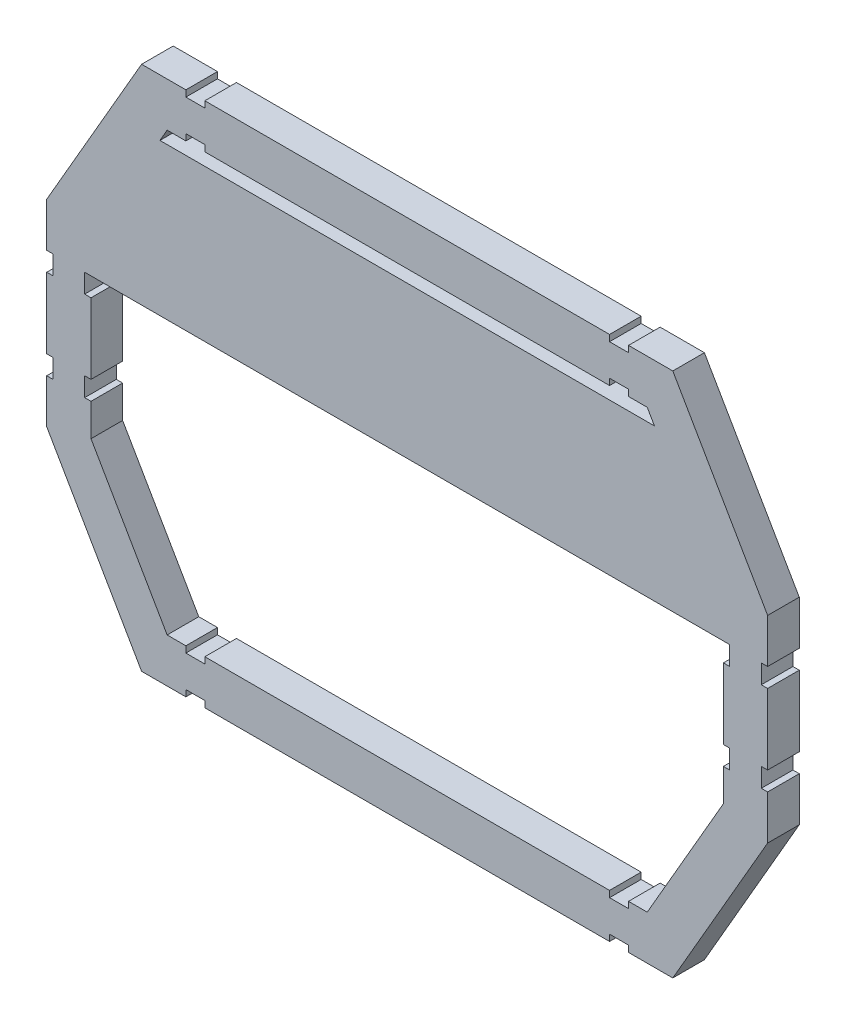
SolidWorks part; units mm, degrees
ref_plane "Plan de face" through (0, 0, 0) normal (0, 0, 1) x (1, 0, 0)
ref_plane "Plan de dessus" through (0, 0, 0) normal (0, 1, 0) x (1, 0, 0)
ref_plane "Plan de droite" through (0, 0, 0) normal (1, 0, 0) x (0, 0, -1)
sketch "Esquisse1" plane through (0, 0, 0) normal (0, 0, 1) x (1, 0, 0)
  line L0 (82.5398, -153.6268) -> (18.5398, -153.6268)
  line L1 (18.5398, -153.6268) -> (18.5398, -152.6268)
  line L2 (18.5398, -152.6268) -> (15.5398, -152.6268)
  line L3 (15.5398, -152.6268) -> (15.5398, -153.6268)
  line L4 (15.5398, -153.6268) -> (8.5398, -153.6268)
  line L5 (8.5398, -153.6268) -> (-6.4602, -127.646)
  line L6 (-6.4602, -127.646) -> (-6.4602, -120.646)
  line L7 (-6.4602, -120.646) -> (-5.4602, -120.646)
  line L8 (-5.4602, -120.646) -> (-5.4602, -117.646)
  line L9 (-5.4602, -117.646) -> (-6.4602, -117.646)
  line L10 (-6.4602, -117.646) -> (-6.4602, -106.4691)
  line L11 (50.5398, -153.6268) -> (50.5398, -70.4883) construction
  line L12 (100.5398, -112.0576) -> (0.5398, -112.0576) construction
  line L13 (1.0398, -140.6364) -> (50.5398, -112.0576) construction
  line L14 (0.5398, -106.4691) -> (0.5398, -117.646)
  line L15 (0.5398, -117.646) -> (-0.4602, -117.646)
  line L16 (-0.4602, -117.646) -> (-0.4602, -120.646)
  line L17 (-0.4602, -120.646) -> (0.5398, -120.646)
  line L18 (0.5398, -120.646) -> (0.5398, -125.7704)
  line L19 (0.5398, -125.7704) -> (12.5813, -146.6268)
  line L20 (12.5813, -146.6268) -> (15.5398, -146.6268)
  line L21 (15.5398, -146.6268) -> (15.5398, -147.6268)
  line L22 (15.5398, -147.6268) -> (18.5398, -147.6268)
  line L23 (18.5398, -147.6268) -> (18.5398, -146.6268)
  line L24 (18.5398, -146.6268) -> (82.5398, -146.6268)
  line L25 (1.0398, -83.4787) -> (50.5398, -112.0576) construction
  line L26 (18.5398, -77.4883) -> (82.5398, -77.4883)
  line L27 (18.5398, -76.4883) -> (18.5398, -77.4883)
  line L28 (15.5398, -76.4883) -> (18.5398, -76.4883)
  line L29 (15.5398, -77.4883) -> (15.5398, -76.4883)
  line L30 (12.5813, -77.4883) -> (15.5398, -77.4883)
  line L31 (88.4984, -77.4883) -> (89.642, -79.4691)
  line L33 (-0.4602, -103.4691) -> (0.5398, -103.4691)
  line L34 (-0.4602, -106.4691) -> (-0.4602, -103.4691)
  line L35 (0.5398, -106.4691) -> (-0.4602, -106.4691)
  line L36 (-5.4602, -106.4691) -> (-6.4602, -106.4691)
  line L37 (-5.4602, -103.4691) -> (-5.4602, -106.4691)
  line L38 (-6.4602, -103.4691) -> (-5.4602, -103.4691)
  line L39 (-6.4602, -96.4691) -> (-6.4602, -103.4691)
  line L40 (8.5398, -70.4883) -> (-6.4602, -96.4691)
  line L41 (15.5398, -70.4883) -> (8.5398, -70.4883)
  line L42 (15.5398, -71.4883) -> (15.5398, -70.4883)
  line L43 (18.5398, -71.4883) -> (15.5398, -71.4883)
  line L44 (18.5398, -70.4883) -> (18.5398, -71.4883)
  line L45 (82.5398, -70.4883) -> (18.5398, -70.4883)
  line L46 (100.0398, -83.4787) -> (50.5398, -112.0576) construction
  line L47 (100.0398, -140.6364) -> (50.5398, -112.0576) construction
  line L48 (82.5398, -70.4883) -> (82.5398, -71.4883)
  line L49 (82.5398, -71.4883) -> (85.5398, -71.4883)
  line L50 (85.5398, -71.4883) -> (85.5398, -70.4883)
  line L51 (85.5398, -70.4883) -> (92.5398, -70.4883)
  line L52 (92.5398, -70.4883) -> (107.5398, -96.4691)
  line L53 (107.5398, -96.4691) -> (107.5398, -103.4691)
  line L54 (107.5398, -103.4691) -> (106.5398, -103.4691)
  line L55 (106.5398, -103.4691) -> (106.5398, -106.4691)
  line L56 (106.5398, -106.4691) -> (107.5398, -106.4691)
  line L57 (100.5398, -106.4691) -> (101.5398, -106.4691)
  line L58 (101.5398, -106.4691) -> (101.5398, -103.4691)
  line L59 (101.5398, -103.4691) -> (100.5398, -103.4691)
  line L62 (88.4984, -77.4883) -> (85.5398, -77.4883)
  line L63 (85.5398, -77.4883) -> (85.5398, -76.4883)
  line L64 (85.5398, -76.4883) -> (82.5398, -76.4883)
  line L65 (82.5398, -76.4883) -> (82.5398, -77.4883)
  line L66 (82.5398, -147.6268) -> (82.5398, -146.6268)
  line L67 (85.5398, -147.6268) -> (82.5398, -147.6268)
  line L68 (85.5398, -146.6268) -> (85.5398, -147.6268)
  line L69 (88.4984, -146.6268) -> (85.5398, -146.6268)
  line L70 (100.5398, -125.7704) -> (88.4984, -146.6268)
  line L71 (100.5398, -120.646) -> (100.5398, -125.7704)
  line L72 (101.5398, -120.646) -> (100.5398, -120.646)
  line L73 (101.5398, -117.646) -> (101.5398, -120.646)
  line L74 (100.5398, -117.646) -> (101.5398, -117.646)
  line L75 (100.5398, -106.4691) -> (100.5398, -117.646)
  line L76 (107.5398, -117.646) -> (107.5398, -106.4691)
  line L77 (106.5398, -117.646) -> (107.5398, -117.646)
  line L78 (106.5398, -120.646) -> (106.5398, -117.646)
  line L79 (107.5398, -120.646) -> (106.5398, -120.646)
  line L80 (107.5398, -127.646) -> (107.5398, -120.646)
  line L81 (92.5398, -153.6268) -> (107.5398, -127.646)
  line L82 (85.5398, -153.6268) -> (92.5398, -153.6268)
  line L83 (85.5398, -152.6268) -> (85.5398, -153.6268)
  line L84 (82.5398, -152.6268) -> (85.5398, -152.6268)
  line L85 (82.5398, -153.6268) -> (82.5398, -152.6268)
  line L86 (0.5398, -103.4691) -> (100.5398, -103.4691)
  line L87 (11.4377, -79.4691) -> (89.642, -79.4691)
  line L88 (12.5813, -77.4883) -> (11.4377, -79.4691)
  point P10 (1.0398, -140.6364)
  point P41 (-6.4602, -112.0576)
  point P73 (50.5398, -77.4883)
  point P74 (50.5398, -146.6268)
  point P75 (50.5398, -146.6268)
  point P94 (107.5398, -112.0576)
  dimension "D1" = 1
  dimension "D2" = 3
  dimension "D3" = 7
  dimension "D4" = 3
  dimension "D5" = 7
  dimension "D6" = 60
  dimension "D7" = 90
  dimension "D8" = 1
  dimension "D9" = 1
  dimension "D10" = 1
  dimension "D11" = 7
  dimension "D12" = 7
  dimension "D13" = 7
  dimension "D14" = 30
  dimension "D15" = 35
  dimension "D16" = 24
extrude "Boss.-Extru.1" add sketch "Esquisse1" along normal blind 5
sketch "Esquisse2" plane through (0, 0, 5) normal (0, 0, 1) x (1, 0, 0)
  line L1 (84.6395, -471.8854) -> (134.6395, -471.8854)
  line L2 (84.6395, -471.8854) -> (84.6395, -521.8854)
  line L3 (84.6395, -521.8854) -> (134.6395, -521.8854)
  line L4 (134.6395, -471.8854) -> (134.6395, -521.8854)
  circle A0 centre (87.1395, -474.3854) radius 1.5
  circle A1 centre (132.1395, -474.3854) radius 1.5
  circle A2 centre (87.1395, -519.3854) radius 1.5
  circle A3 centre (132.1395, -519.3854) radius 1.5
  dimension "D1" = 2.5
  dimension "D2" = 2.5
  dimension "D5" = 50
  dimension "D6" = 50
  dimension "D3" = 2
  dimension "D4" = 2
